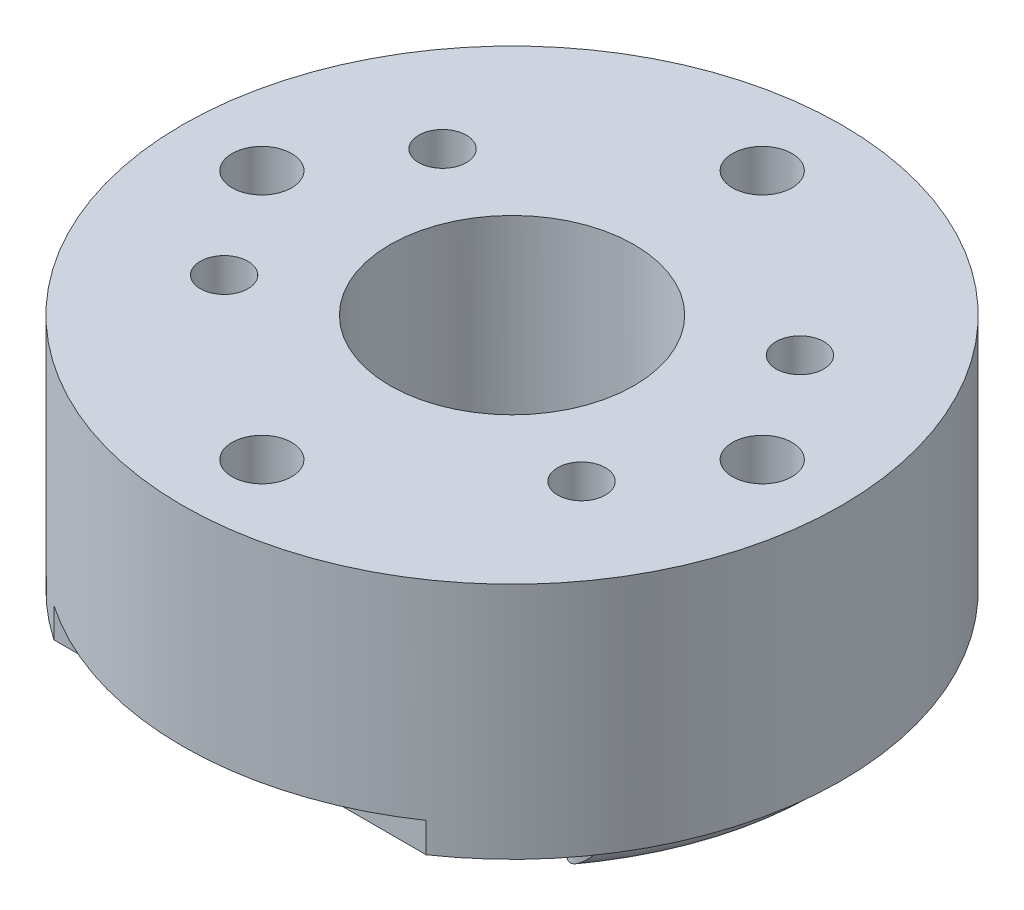
SolidWorks part; units mm, degrees
ref_plane "Front Plane" through (0, 0, 0) normal (0, 0, 1) x (1, 0, 0)
ref_plane "Top Plane" through (0, 0, 0) normal (0, 1, 0) x (1, 0, 0)
ref_plane "Right Plane" through (0, 0, 0) normal (1, 0, 0) x (0, 0, -1)
sketch "Sketch1" plane through (0, 0, 0) normal (0, 1, 0) x (1, 0, 0)
  arc A0 (17.6, 0) -> (-17.6, 0) centre (0, 0) ccw construction
  arc A1 (17.6, 0) -> (-17.6, 0) centre (0, 0) ccw
  circle A2 centre (0, 0) radius 12.6 construction
  circle A3 centre (0, 0) radius 12.6
ref_plane "Plane1" through (0, -12, 0) normal (0, 1, 0) x (1, 0, 0)
sketch "Sketch2" plane through (0, -12, 0) normal (0, 1, 0) x (1, 0, 0)
  line L4 (-11, 7.5) -> (-11, -20.5)
  line L5 (-11, -20.5) -> (11, -20.5)
  line L6 (11, -20.5) -> (11, 7.5)
  line L7 (11, 7.5) -> (-11, 7.5)
  line L8 (-11, 7.5) -> (-11, -20.5)
  line L9 (-11, -20.5) -> (11, -20.5)
  line L10 (11, -20.5) -> (11, 7.5)
  line L11 (11, 7.5) -> (-11, 7.5)
  line L16 (2.58, 2.15) -> (-2.58, 2.15)
  line L17 (2.58, -2.15) -> (2.58, 2.15)
  line L18 (-2.58, -2.15) -> (2.58, -2.15)
  line L19 (-2.58, 2.15) -> (-2.58, -2.15)
  line L20 (2.58, 2.15) -> (-2.58, 2.15)
  line L21 (2.58, -2.15) -> (2.58, 2.15)
  line L22 (-2.58, -2.15) -> (2.58, -2.15)
  line L23 (-2.58, 2.15) -> (-2.58, -2.15)
  circle A0 centre (9, -5.5) radius 1.3 construction
  circle A1 centre (9, 5.5) radius 1.3 construction
  circle A2 centre (-9, 5.5) radius 1.3 construction
  circle A3 centre (-9, -5.5) radius 1.3 construction
  circle A4 centre (9, -5.5) radius 1.3
  circle A5 centre (9, 5.5) radius 1.3
  circle A6 centre (-9, 5.5) radius 1.3
  circle A7 centre (-9, -5.5) radius 1.3
  dimension "D1" = 0
  dimension "D2" = 0
ref_plane "Plane2" through (0, -10, 0) normal (0, -1, 0) x (-1, 0, 0)
sketch "Sketch3" plane through (0, -10, 0) normal (0, -1, 0) x (-1, 0, 0)
  circle A0 centre (0, 0) radius 5.15 construction
  circle A1 centre (0, 0) radius 5.15
sketch "Sketch4" plane through (0, 0, 0) normal (0, 1, 0) x (1, 0, 0)
  circle A0 centre (0, 0) radius 16.6
  arc A1 (17.6, 0) -> (-17.6, 0) centre (0, 0) ccw construction
  circle A2 centre (0, 0) radius 5.15 construction
  circle A3 centre (0, 0) radius 5.15 construction
  circle A4 centre (0, 0) radius 6.15
  dimension "D1" = 1
  dimension "D2" = 1
extrude "Boss-Extrude1" add sketch "Sketch4" against normal up to surface (12 mm away) up to plane "Plane1"
sketch "Sketch5" plane through (0, -12, 0) normal (0, -1, 0) x (1, 0, 0)
  line L0 (11, 20.5) -> (11, -7.5) construction
  line L1 (11, -7.5) -> (-11, -7.5) construction
  line L2 (-11, -7.5) -> (-11, 20.5) construction
  line L3 (11, 11.0616) -> (11, -7.5) construction
  line L4 (11, -7.5) -> (-11, -7.5) construction
  line L5 (-11, -7.5) -> (-11, 11.0616) construction
  line L6 (11.2, 10.8591) -> (11.2, -7.7)
  line L7 (11.2, -7.7) -> (-11.2, -7.7)
  line L8 (-11.2, -7.7) -> (-11.2, 10.8591)
  line L9 (-11.2, -7.7) -> (-11.2, 20.5) construction
  line L10 (-11, -7.5) -> (-11, 20.5) construction
  line L11 (11, 20.5) -> (11, -7.5) construction
  line L12 (11.2, 20.5) -> (11.2, -7.7) construction
  arc A0 (-11.2, 10.8591) -> (11.2, 10.8591) centre (0, 0) ccw
  dimension "D1" = 0.2
extrude "Boss-Extrude2" add sketch "Sketch5" along normal blind 1.5
sketch "Sketch6" plane through (0, -12, 0) normal (0, -1, 0) x (1, 0, 0)
  circle A0 centre (9, -5.5) radius 1.2
  circle A1 centre (9, 5.5) radius 1.2
  circle A2 centre (-9, 5.5) radius 1.2
  circle A3 centre (-9, -5.5) radius 1.2
  dimension "D1" = 2.4
extrude "Cut-Extrude1" cut sketch "Sketch6" against normal through all
sketch "Sketch7" plane through (0, 0, 0) normal (0, 1, 0) x (1, 0, 0)
  line L0 (0, 12.6) -> (0, -12.6) construction
  line L1 (-12.6, 0) -> (12.6, 0) construction
  circle A0 centre (0, 0) radius 12.6 construction
  circle A1 centre (0, 0) radius 16.6 construction
  circle A2 centre (0, 12.6) radius 1.5
  circle A3 centre (12.6, 0) radius 1.5
  circle A4 centre (-12.6, 0) radius 1.5
  circle A5 centre (0, -12.6) radius 1.5
  dimension "D1" = 4
  dimension "D2" = 3
extrude "Cut-Extrude2" cut sketch "Sketch7" against normal through all
fillet "Fillet1" radius 1 2 edges at (-11.2, -12.75, 10.8591) (11.2, -12.75, 10.8591)
fillet "Fillet2" radius 1 1 edges at (0, -13.5, -15.6) tangent propagation no
sketch "Sketch8" plane through (0, -12, 0) normal (0, -1, 0) x (1, 0, 0)
  line L4 (-2.58, -2.15) -> (2.58, -2.15)
  line L5 (-2.58, 2.15) -> (-2.58, -2.15)
  line L6 (2.58, 2.15) -> (-2.58, 2.15)
  line L7 (2.58, -2.15) -> (2.58, 2.15)
  line L8 (-2.58, -2.15) -> (2.58, -2.15) construction
  line L9 (-2.58, 2.15) -> (-2.58, -2.15) construction
  line L10 (2.58, 2.15) -> (-2.58, 2.15) construction
  line L11 (2.58, -2.15) -> (2.58, 2.15) construction
  line L12 (-11, 20.5) -> (-11, -7.5)
  line L13 (11, 20.5) -> (-11, 20.5)
  line L14 (11, -7.5) -> (11, 20.5)
  line L15 (-11, -7.5) -> (11, -7.5)
  line L16 (-11, 20.5) -> (-11, -7.5) construction
  line L17 (11, 20.5) -> (-11, 20.5) construction
  line L18 (11, -7.5) -> (11, 20.5) construction
  line L19 (-11, -7.5) -> (11, -7.5) construction
  line L22 (3.35, 11.5) -> (-5.2, 11.5)
  line L23 (3.35, 4.5) -> (3.35, 11.5)
  line L28 (10, 18.7) -> (-10, 18.7)
  line L29 (10, 13.7) -> (10, 18.7)
  line L30 (-10, 13.7) -> (10, 13.7)
  line L31 (-10, 18.7) -> (-10, 13.7)
  line L32 (10, 18.7) -> (-10, 18.7)
  line L33 (10, 13.7) -> (10, 18.7)
  line L34 (-10, 13.7) -> (10, 13.7)
  line L35 (-10, 18.7) -> (-10, 13.7)
  line L36 (-3.65, 4.5) -> (3.35, 4.5)
  line L37 (-3.65, 9) -> (-3.65, 4.5)
  line L38 (-5.2, 9) -> (-3.65, 9)
  line L39 (-5.2, 11.5) -> (-5.2, 9)
  line L40 (3.35, 11.5) -> (-5.2, 11.5)
  line L41 (3.35, 4.5) -> (3.35, 11.5)
  line L42 (-3.65, 4.5) -> (3.35, 4.5)
  line L43 (-3.65, 9) -> (-3.65, 4.5)
  line L44 (-5.2, 9) -> (-3.65, 9)
  line L45 (-5.2, 11.5) -> (-5.2, 9)
  dimension "D1" = 0
  dimension "D2" = 0
  dimension "D3" = 0
  dimension "D4" = 0
extrude "Cut-Extrude3" cut sketch "Sketch8" against normal blind 1.5
